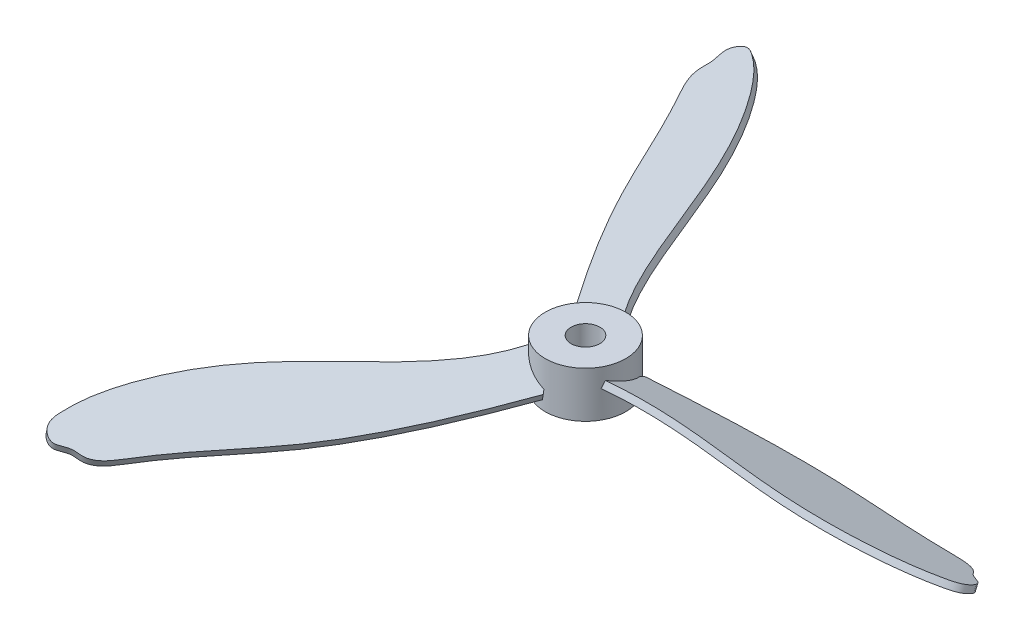
SolidWorks part; units mm, degrees
ref_plane "Front Plane" through (0, 0, 0) normal (0, 0, 1) x (1, 0, 0)
ref_plane "Top Plane" through (0, 0, 0) normal (0, 1, 0) x (1, 0, 0)
ref_plane "Right Plane" through (0, 0, 0) normal (1, 0, 0) x (0, 0, -1)
sketch "Sketch1" plane through (0, 0, 0) normal (0, 1, 0) x (1, 0, 0)
  circle A0 centre (0, 0) radius 7
  circle A1 centre (0, 0) radius 2.5
extrude "Boss-Extrude1" add sketch "Sketch1" along normal blind 4 and the other way blind 4
ref_plane "Plane1" through (0, 0, 0) normal (0, -0.7071, 0.7071) x (1, 0, 0)
ref_plane "Plane2" through (0, 0, 0) normal (0, -0.9239, 0.3827) x (-1, 0, 0)
sketch "Sketch2" plane through (0, 0, 0) normal (0, -0.9239, 0.3827) x (-1, 0, 0)
  line L0 (-6.4426, 4.0596) -> (-3.5194, -4.0596)
  line L1 (-4.981, 0) -> (0, 0) construction
  line L2 (-4.981, 0) -> (-67.981, 0) construction
  ellipse E0 centre (0, 1.5307) end of major axis (-7, 1.5307) minor radius 6.4672 construction
  spline S0 degree 3 poles (-6.4426, 4.0596) (-16.8501, 5.362) (-35.2793, 7.0537) (-53.2832, 3.8705) (-64.0155, 4.0682) (-65.9051, 1.0503) (-68.424, 0.5312) (-68.2679, -2.7746) (-63.9598, -5.1014) (-54.6879, -7.4212) (-33.3511, -7.4951) (-15.5737, -0.617) (-3.5194, -4.0596) knots 0 0 0 0 0.246203 0.401237 0.448756 0.459405 0.479965 0.497386 0.519085 0.584946 0.719403 1 1 1 1
  dimension "D1" = 63
extrude "Boss-Extrude2" add sketch "Sketch2" along normal blind 0.6 and the other way blind 0.6
pattern_circular "CirPattern1" count 3 every 120 about axis through (0, -4, 0) along (0, 1, 0) of "Boss-Extrude2"
